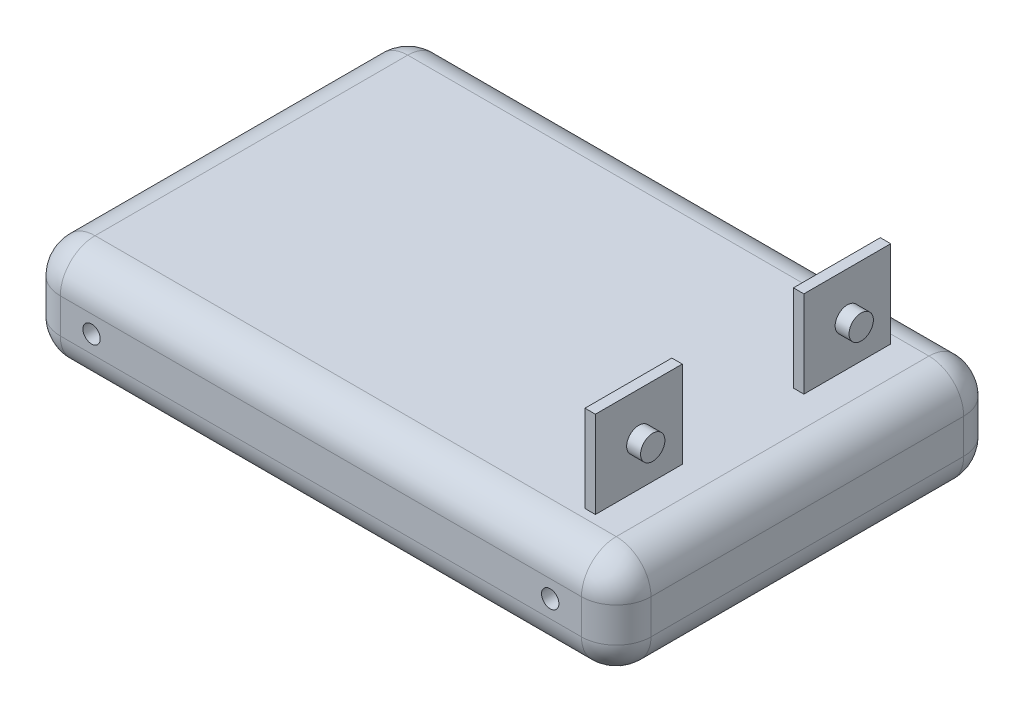
SolidWorks part; units mm, degrees
ref_plane "Front Plane" through (0, 0, 0) normal (0, 0, 1) x (1, 0, 0)
ref_plane "Top Plane" through (0, 0, 0) normal (0, 1, 0) x (1, 0, 0)
ref_plane "Right Plane" through (0, 0, 0) normal (1, 0, 0) x (0, 0, -1)
sketch "Sketch1" plane through (0, 0, 0) normal (0, 1, 0) x (1, 0, 0)
  line L1 (-85, 55) -> (85, 55)
  line L2 (-85, 55) -> (-85, -55)
  line L3 (-85, -55) -> (85, -55)
  line L4 (85, 55) -> (85, -55)
  line L5 (-85, 55) -> (85, -55) construction
  line L6 (-85, -55) -> (85, 55) construction
  point P0 (0, 0)
  dimension "D1" = 170
  dimension "D2" = 110
extrude "Boss-Extrude1" add sketch "Sketch1" along normal blind 30
fillet "Fillet2" radius 10 5 edges at (-85, 15, 55) (0, 30, 55) (85, 15, 55) (0, 0, 55) (-85, 30, 0)
fillet "Fillet3" radius 10 6 edges at (82.0711, 27.0711, 52.0711) (-85, 10, -55) (-82.0711, 27.0711, -55) (85, 30, -5) (85, 15, -55) (5, 30, -55)
fillet "Fillet4" radius 10 7 edges at (82.0711, 2.9289, 52.0711) (-82.0711, 2.9289, 52.0711) (-85, 0, 0) (-82.0711, 0, -52.0711) (82.0711, 0, -52.0711) (0, 0, -55) (85, 0, 0)
sketch "Sketch3" plane through (0, 0, -55) normal (0, 0, -1) x (-1, 0, 0)
  line L0 (-75, 15) -> (75, 15) construction
  line L1 (-75, 20) -> (-75, 10) construction
  line L2 (75, 10) -> (75, 20) construction
  line L3 (-66, 20) -> (-66, 10) construction
  line L4 (75, 20) -> (-75, 20) construction
  line L5 (-75, 10) -> (75, 10) construction
  line L6 (66, 20) -> (66, 10) construction
  circle A0 centre (-66, 15) radius 2.5
  circle A1 centre (66, 15) radius 2.5
extrude "Cut-Extrude1" cut sketch "Sketch3" against normal blind 5
sketch "Sketch5" plane through (0, 0, 55) normal (0, 0, 1) x (1, 0, 0)
  line L0 (-75, 15) -> (75, 15) construction
  line L1 (-75, 20) -> (-75, 10) construction
  line L2 (75, 10) -> (75, 20) construction
  line L3 (-66, 20) -> (-66, 10) construction
  line L4 (75, 20) -> (-75, 20) construction
  line L5 (-75, 10) -> (75, 10) construction
  line L6 (66, 20) -> (66, 10) construction
  circle A0 centre (-66, 15) radius 2.5
  circle A1 centre (66, 15) radius 2.5
  dimension "D1" = 9
  dimension "D2" = 9
extrude "Cut-Extrude2" cut sketch "Sketch5" against normal blind 5
sketch "Sketch6" plane through (0, 30, 0) normal (0, 1, 0) x (1, 0, 0)
  line L0 (-75, 0) -> (75, 0) construction
  line L1 (-75, 45) -> (-75, -45) construction
  line L2 (75, -45) -> (75, 45) construction
  line L3 (65, 45) -> (65, -45) construction
  line L4 (75, 45) -> (-75, 45) construction
  line L5 (-75, -45) -> (75, -45) construction
  line L6 (75, 30) -> (-75, 30) construction
  line L7 (-75, -30) -> (75, -30) construction
  line L9 (63.5, 42.5) -> (66.5, 42.5)
  line L10 (63.5, 42.5) -> (63.5, 17.5)
  line L11 (63.5, 17.5) -> (66.5, 17.5)
  line L12 (66.5, 42.5) -> (66.5, 17.5)
  line L13 (63.5, 42.5) -> (66.5, 17.5) construction
  line L14 (63.5, 17.5) -> (66.5, 42.5) construction
  line L15 (63.5, -42.5) -> (66.5, -42.5)
  line L16 (63.5, -42.5) -> (63.5, -17.5)
  line L17 (63.5, -17.5) -> (66.5, -17.5)
  line L18 (66.5, -42.5) -> (66.5, -17.5)
  line L19 (63.5, -42.5) -> (66.5, -17.5) construction
  line L20 (63.5, -17.5) -> (66.5, -42.5) construction
  point P16 (65, 30)
  point P21 (65, -30)
extrude "Boss-Extrude2" add sketch "Sketch6" along normal blind 25
sketch "Sketch7" plane through (66.5, 0, 0) normal (1, 0, 0) x (0, 0, -1)
  line L0 (-30, 55) -> (-30, 30) construction
  line L1 (-42.5, 55) -> (-17.5, 55) construction
  line L2 (-42.5, 30) -> (-17.5, 30) construction
  line L3 (-42.5, 42.5) -> (-17.5, 42.5) construction
  line L4 (-42.5, 55) -> (-42.5, 30) construction
  line L5 (-17.5, 55) -> (-17.5, 30) construction
  circle A0 centre (-30, 42.5) radius 3.5
extrude "Boss-Extrude3" add sketch "Sketch7" along normal blind 4
sketch "Sketch8" plane through (66.5, 0, 0) normal (1, 0, 0) x (0, 0, -1)
  line L0 (30, 55) -> (30, 30) construction
  line L1 (17.5, 55) -> (42.5, 55) construction
  line L2 (17.5, 30) -> (42.5, 30) construction
  line L3 (17.5, 42.5) -> (42.5, 42.5) construction
  line L4 (17.5, 55) -> (17.5, 30) construction
  line L5 (42.5, 55) -> (42.5, 30) construction
  circle A0 centre (30, 42.5) radius 3.5
extrude "Boss-Extrude4" add sketch "Sketch8" along normal blind 4
